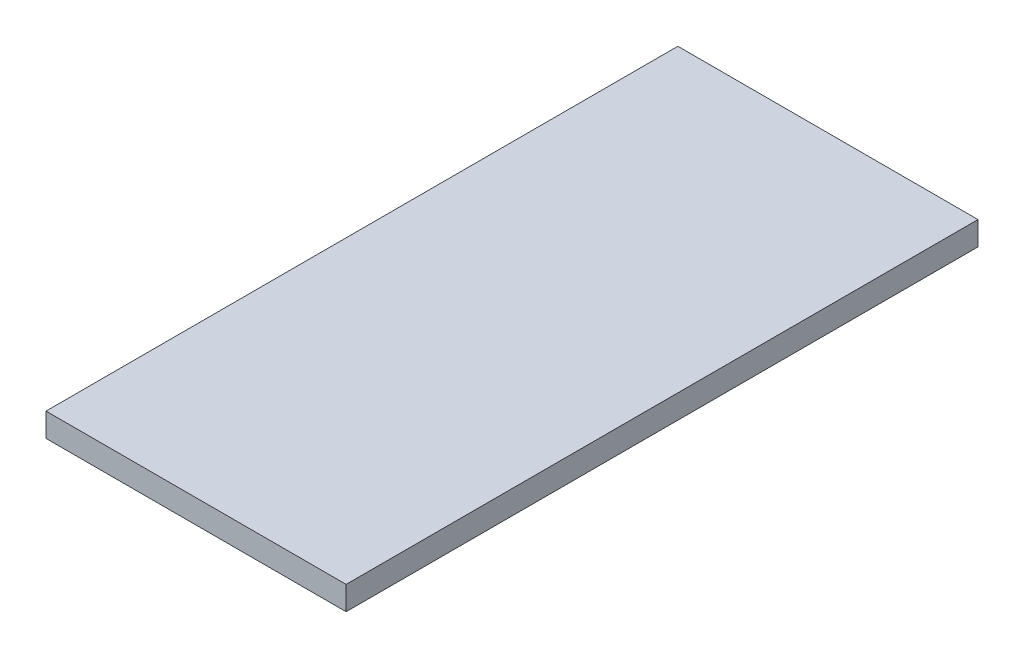
SolidWorks part; units mm, degrees
ref_plane "Front Plane" through (0, 0, 0) normal (0, 0, 1) x (1, 0, 0)
ref_plane "Top Plane" through (0, 0, 0) normal (0, 1, 0) x (1, 0, 0)
ref_plane "Right Plane" through (0, 0, 0) normal (1, 0, 0) x (0, 0, -1)
sketch "Sketch1" plane through (0, 0, 0) normal (0, 1, 0) x (1, 0, 0)
  line L1 (120.65, -254) -> (-120.65, -254)
  line L2 (120.65, -254) -> (120.65, 254)
  line L3 (120.65, 254) -> (-120.65, 254)
  line L4 (-120.65, -254) -> (-120.65, 254)
  line L5 (120.65, -254) -> (-120.65, 254) construction
  line L6 (120.65, 254) -> (-120.65, -254) construction
  point P0 (0, 0)
  dimension "D1" = 241.3
  dimension "D2" = 508
extrude "Boss-Extrude1" add sketch "Sketch1" along normal mid plane 19.05
